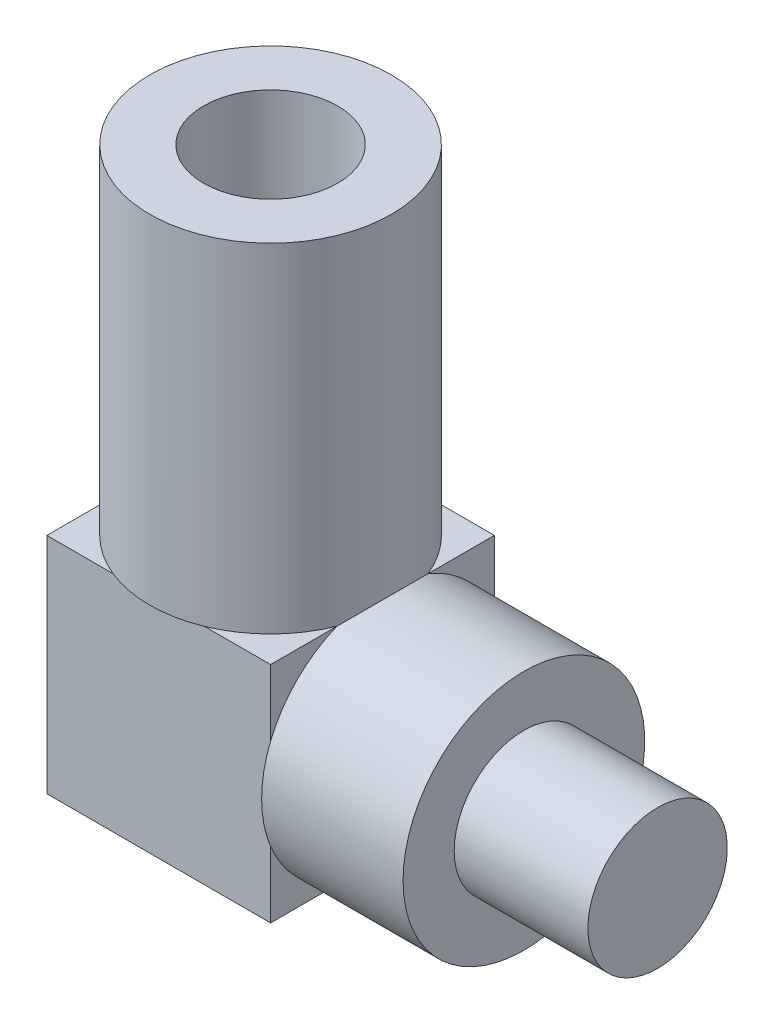
SolidWorks part; units mm, degrees
ref_plane "Front Plane" through (0, 0, 0) normal (0, 0, 1) x (1, 0, 0)
ref_plane "Top Plane" through (0, 0, 0) normal (0, 1, 0) x (1, 0, 0)
ref_plane "Right Plane" through (0, 0, 0) normal (1, 0, 0) x (0, 0, -1)
sketch "Block Sketch" plane through (0, 0, 0) normal (0, 0, 1) x (1, 0, 0)
  line L0 (-25.95, -7.95) -> (-10.05, -7.95)
  line L1 (-10.05, -7.95) -> (-10.05, 7.95)
  line L2 (-10.05, 7.95) -> (-25.95, 7.95)
  line L3 (-25.95, 7.95) -> (-25.95, -7.95)
extrude "Block" add sketch "Block Sketch" along normal mid plane 15.9
ref_axis "Engine Axis" through (11.3043, 0, 0) along (-1, 0, 0)
sketch "Neck and Stud Sketch" plane through (0, 0, 0) normal (0, 0, 1) x (1, 0, 0)
  line L0 (-1000, 0) -> (1000, 0) construction
  line L1 (9.5, 0) -> (9.5, 4.953)
  line L2 (9.5, 4.953) -> (0, 4.953)
  line L3 (0, 4.953) -> (0, 8.586)
  line L4 (0, 8.586) -> (-10.05, 8.586)
  line L5 (-10.05, 8.586) -> (-10.05, 0)
  line L6 (-10.05, 0) -> (9.5, 0)
revolve "Neck and Stud" add sketch "Neck and Stud Sketch" angle 360 about L0
sketch "Arm Sketch" plane through (0, 0, 0) normal (0, 0, 1) x (1, 0, 0)
  line L0 (-18, 0) -> (-18, 500) construction
  line L1 (-18, 7.95) -> (-9.414, 7.95)
  line L2 (-9.414, 7.95) -> (-9.414, 32)
  line L3 (-9.414, 32) -> (-18, 32)
  line L4 (-18, 32) -> (-18, 7.95)
revolve "Arm" add sketch "Arm Sketch" angle 360 about L0
sketch "Socket Sketch" plane through (0, 0, 0) normal (0, 0, 1) x (1, 0, 0)
  line L0 (-18, 0) -> (-18, 500) construction
  line L1 (-18, 15.2) -> (-13.2375, 15.2)
  line L2 (-13.2375, 15.2) -> (-13.2375, 33)
  line L3 (-13.2375, 33) -> (-18, 33)
  line L4 (-18, 33) -> (-18, 15.2)
revolve "Socket" cut sketch "Socket Sketch" angle 360 about L0
